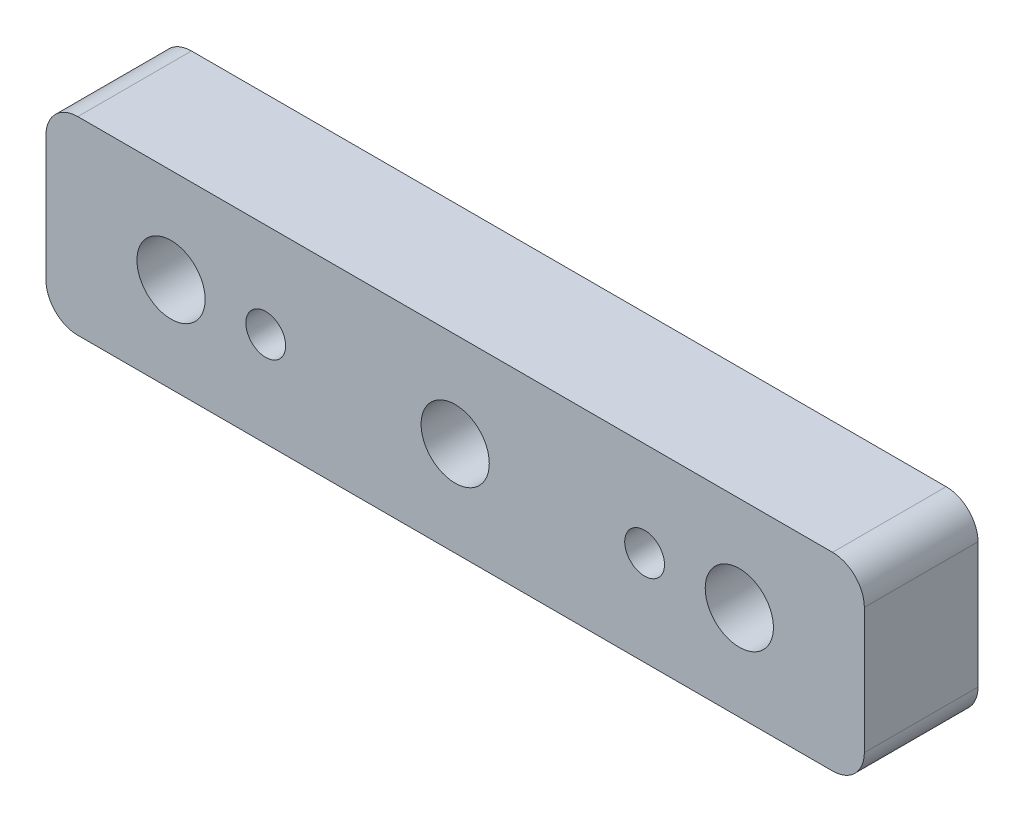
SolidWorks part; units mm, degrees
material "6061-T6 (SS)"
ref_plane "Front Plane" through (0, 0, 0) normal (0, 0, 1) x (1, 0, 0)
ref_plane "Top Plane" through (0, 0, 0) normal (0, 1, 0) x (1, 0, 0)
ref_plane "Right Plane" through (0, 0, 0) normal (1, 0, 0) x (0, 0, -1)
sketch "Sketch1" plane through (0, 0, 0) normal (0, 0, 1) x (1, 0, 0)
  line L1 (39.84, -10) -> (-39.84, -10)
  line L2 (43.2, -6.64) -> (43.2, 6.64)
  line L3 (39.84, 10) -> (-39.84, 10)
  line L4 (-43.2, -6.64) -> (-43.2, 6.64)
  line L5 (43.2, -10) -> (-43.2, 10) construction
  line L6 (43.2, 10) -> (-43.2, -10) construction
  arc A0 (43.2, 6.64) -> (39.84, 10) centre (39.84, 6.64) ccw
  arc A1 (39.84, -10) -> (43.2, -6.64) centre (39.84, -6.64) ccw
  arc A2 (-39.84, -10) -> (-43.2, -6.64) centre (-39.84, -6.64) cw
  arc A3 (-39.84, 10) -> (-43.2, 6.64) centre (-39.84, 6.64) ccw
  point P0 (0, 0)
  dimension "D2" = 3.36
  dimension "D1" = 20
  dimension "D3" = 86.4
extrude "Boss-Extrude1" add sketch "Sketch1" along normal blind 12
sketch "Sketch3" plane through (0, 0, 12) normal (0, 0, 1) x (1, 0, 0)
  line L0 (0, 0) -> (0, -10) construction
  line L2 (-39.84, -10) -> (39.84, -10) construction
  circle A0 centre (-30, 0) radius 3.6
  circle A1 centre (30, 0) radius 3.6
  circle A2 centre (0, 0) radius 3.6
  dimension "D1" = 7.2
  dimension "D2" = 60
extrude "Cut-Extrude2" cut sketch "Sketch3" against normal through all
hole_wizard "M5x0.8 Tapped Hole1" positions "Sketch5" profile "Sketch4" tap size "M5x0.8" standard "ANSI Metric" end condition through all
sketch "Sketch5" plane through (0, 0, 12) normal (0, 0, 1) x (1, 0, 0)
  line L0 (0, 10) -> (0, 17.067) construction
  line L1 (39.84, 10) -> (-39.84, 10) construction
  point P0 (-20, 0)
  point P10 (20, 0)
  dimension "D1" = 40
sketch "Sketch4" plane through (-20, 0, 12) normal (1, 0, 0) x (0, -1, 0)
  line L0 (0, 0) -> (0, 12)
  line L1 (0, 12) -> (2.1, 12)
  line L2 (2.1, 12) -> (2.1, 0)
  line L5 (2.1, 0) -> (0, 0)
  line L11 (0, -6.35) -> (0, 107.95) construction
  dimension "Thread Major Dia." = 4.2
  dimension "Thru Tap Drill Depth" = 12
